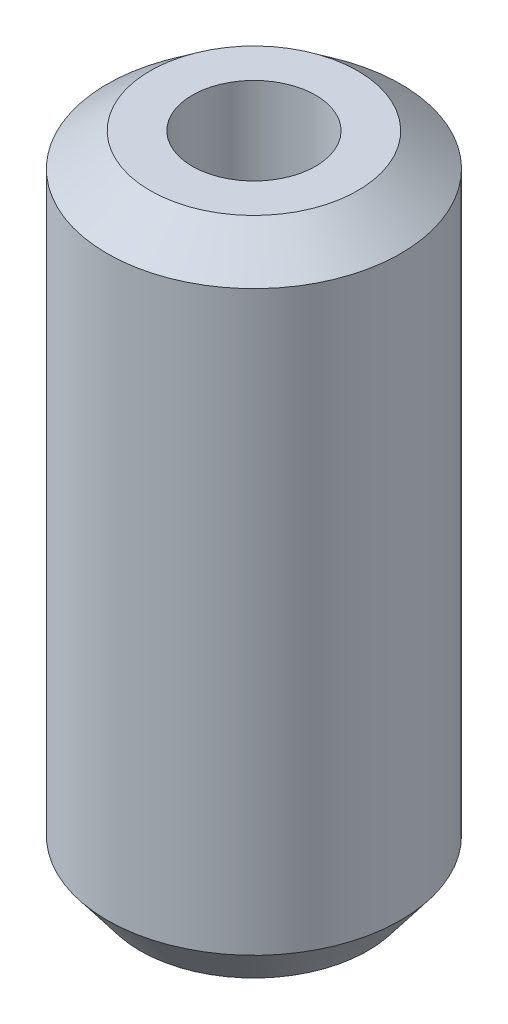
SolidWorks part; units mm, degrees
ref_plane "Front Plane" through (0, 0, 0) normal (0, 0, 1) x (1, 0, 0)
ref_plane "Top Plane" through (0, 0, 0) normal (0, 1, 0) x (1, 0, 0)
ref_plane "Right Plane" through (0, 0, 0) normal (1, 0, 0) x (0, 0, -1)
sketch "Sketch1" plane through (0, 0, 0) normal (0, 1, 0) x (1, 0, 0)
  circle A0 centre (0, 0) radius 10
  dimension "SHAFT_OD" = 20
extrude "Boss-Extrude1" add sketch "Sketch1" along normal blind 44.51
sketch "Sketch2" plane through (0, 0, 0) normal (0, 1, 0) x (1, 0, 0)
  circle A0 centre (0, 0) radius 4.1996
  dimension "BORE_D" = 8.3992
extrude "Cut-Extrude1" cut sketch "Sketch2" along normal through all
chamfer "Chamfer1" distance 2.2478 angle 52.498 2 edges at (0, 44.51, 10) (0, 0, 10) first distance on face at (0, 44.51, 10) first distance on face at (0, 0, 4.1996)
